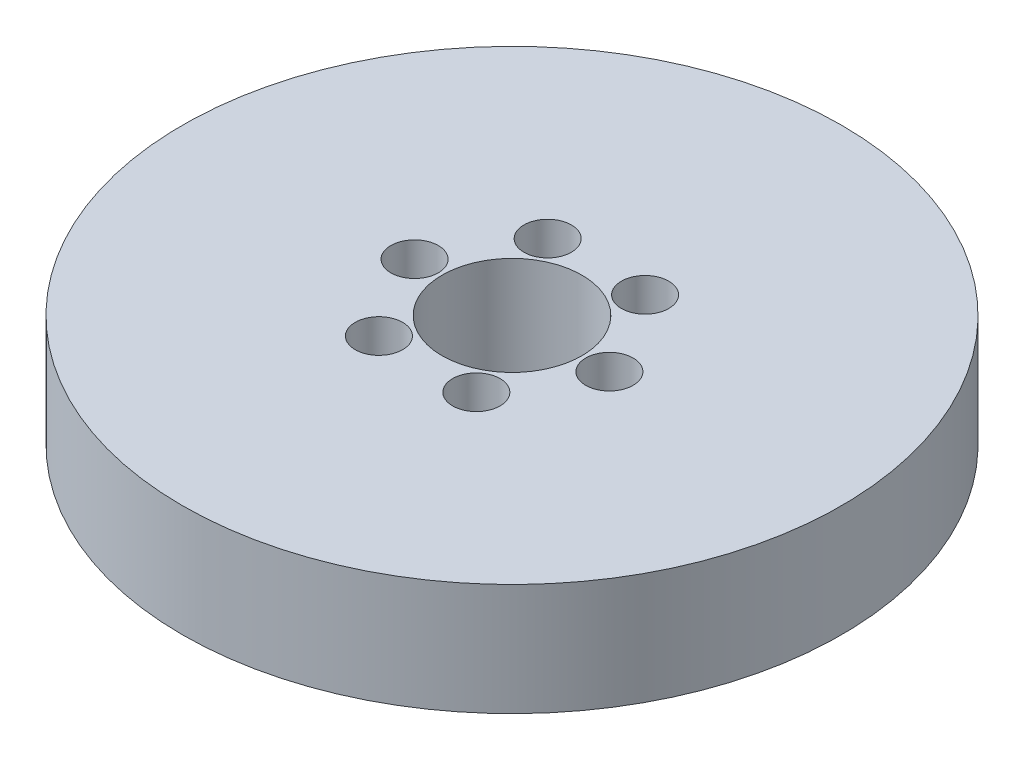
SolidWorks part; units mm, degrees
ref_plane "Front Plane" through (0, 0, 0) normal (0, 0, 1) x (1, 0, 0)
ref_plane "Top Plane" through (0, 0, 0) normal (0, 1, 0) x (1, 0, 0)
ref_plane "Right Plane" through (0, 0, 0) normal (1, 0, 0) x (0, 0, -1)
sketch "Sketch1" plane through (0, 0, 0) normal (0, 1, 0) x (1, 0, 0)
  circle A0 centre (0, 0) radius 82.5
  dimension "FLANGE_OD" = 165
extrude "Boss-Extrude1" add sketch "Sketch1" along normal blind 28
sketch "Sketch2" plane through (0, 0, 0) normal (0, 1, 0) x (1, 0, 0)
  circle A0 centre (0, 0) radius 17.5
  dimension "BORE_D" = 35
extrude "Cut-Extrude1" cut sketch "Sketch2" along normal through all
sketch "Sketch3" plane through (0, 28, 0) normal (0, 1, 0) x (1, 0, 0)
  circle A0 centre (0, 0) radius 24.3873 construction
  circle A1 centre (-24.3873, 0) radius 5.9366
  dimension "BOLT_D" = 11.8733
  dimension "BOLT_PCD" = 48.7747
extrude "Cut-Extrude2" cut sketch "Sketch3" against normal blind 18.4677
pattern_circular "CirPattern1" count 6 over 360 about axis through (0, 0, 0) along (0, 1, 0) of "Cut-Extrude2"
